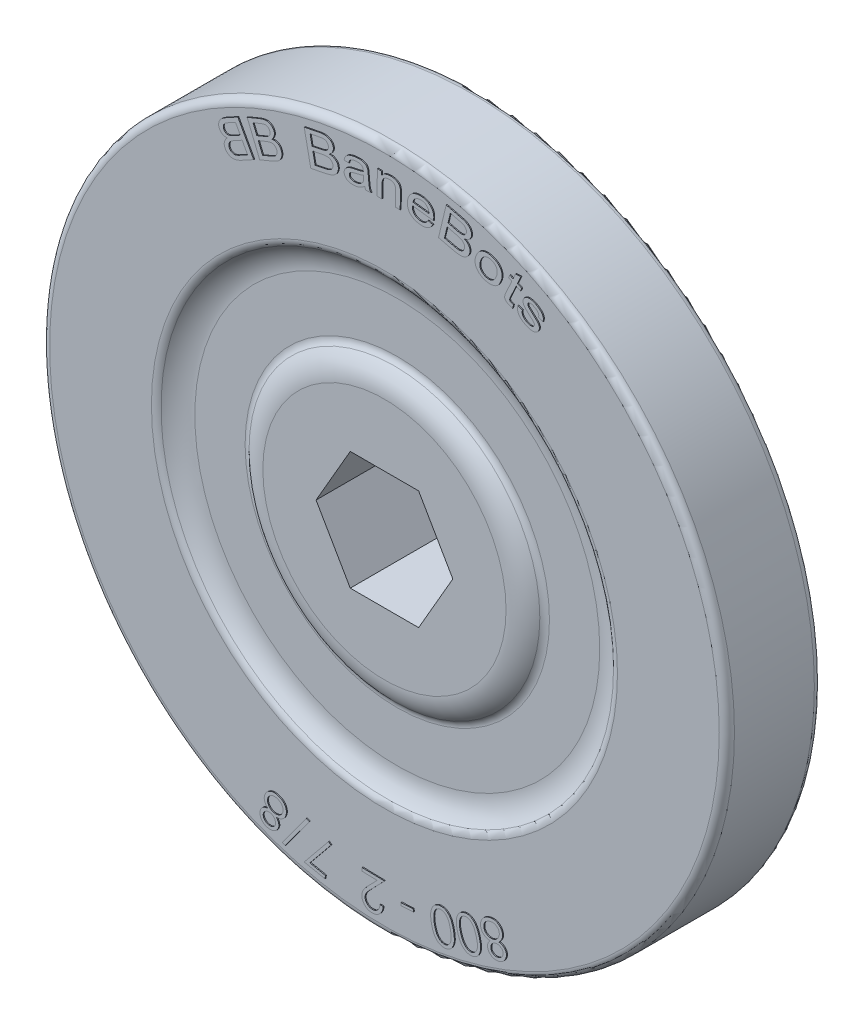
SolidWorks part; units mm, degrees
ref_plane "Front Plane" through (0, 0, 0) normal (0, 0, 1) x (1, 0, 0)
ref_plane "Top Plane" through (0, 0, 0) normal (0, 1, 0) x (1, 0, 0)
ref_plane "Right Plane" through (0, 0, 0) normal (1, 0, 0) x (0, 0, -1)
sketch "Sketch1" plane through (0, 0, 0) normal (0, 0, 1) x (1, 0, 0)
  line L1 (3.594, -6.225) -> (7.188, 0)
  line L2 (7.188, 0) -> (3.594, 6.225)
  line L3 (3.594, 6.225) -> (-3.594, 6.225)
  line L4 (-3.594, 6.225) -> (-7.188, 0)
  line L5 (-7.188, 0) -> (-3.594, -6.225)
  line L6 (-3.594, -6.225) -> (3.594, -6.225)
  circle A0 centre (0, 0) radius 6.225 construction
  circle A1 centre (0, 0) radius 36
  dimension "D1" = 12.45
  dimension "D2" = 72
extrude "Extrude1" add sketch "Sketch1" along normal mid plane 10
fillet "Fillet1" radius 0.8 2 edges at (36, 0, -5) (36, 0, 5)
sketch "Sketch2" plane through (0, 0, 0) normal (0, 1, 0) x (1, 0, 0)
  line L0 (0, 10.15) -> (0, 8.65)
  line L1 (0, 8.65) -> (-15, 8.65)
  line L2 (-15, 8.65) -> (-15, 3.65)
  line L3 (-15, 3.65) -> (-23.5, 3.65)
  line L4 (-23.5, 3.65) -> (-23.5, 10.14)
  line L5 (-23.5, 10.14) -> (-28.5, 10.14)
  line L6 (-28.5, 10.14) -> (-28.5, 10.15)
  line L8 (-28.5, 10.15) -> (0, 10.15)
  dimension "D1" = 0.01
  dimension "D2" = 15
  dimension "D3" = 23.5
  dimension "D4" = 6.5
  dimension "D5" = 1.5
  dimension "D6" = 28.5
revolve "Cut-Revolve1" cut sketch "Sketch2" angle 360 about L0
fillet "Fillet2" radius 1 2 edges at (23.5, 0, -5) (-15, 0, -3.65)
fillet "Fillet3" radius 3.5 2 edges at (-23.5, 0, -3.65) (15, 0, -5)
mirror "Symétrie1" about plane through (0, 0, 0) normal (0, 0, 1) of "Cut-Revolve1", "Fillet2", "Fillet3"
sketch "Sketch4" plane through (0, 0, -5) normal (0, 0, -1) x (-1, 0, 0)
  line L0 (0, 0) -> (-8.33, 29.8599) construction
  line L1 (-13.3409, 27.9825) -> (-15.1484, 31.7737) construction
  line L3 (0, 0) -> (16.4149, 26.2973) construction
  line L4 (0, 0) -> (0, 28.5) construction
  line L5 (0, 0) -> (-16.4149, 26.2973) construction
  line L6 (0, -31) -> (0, 0) construction
  arc A0 (16.4149, 26.2973) -> (-8.33, 29.8599) centre (0, 0) ccw construction
  arc A1 (-10.0963, 29.3098) -> (-16.4149, 26.2973) centre (0, 0) ccw construction
  circle A2 centre (0, 0) radius 35.2 construction
  arc A5 (12.7, -28.2791) -> (-12.7, -28.2791) centre (0, 0) cw construction
  text T0 "BaneBots" font "Arial" height 3.5
  text T1 "800 - 2  7/8"
  dimension "D1" = 62
  dimension "D2" = 25
  dimension "D3" = 7
  dimension "D4" = 1.85
  dimension "D5" = 25.4
extrude "Extrude3" add sketch "Sketch4" along normal blind 0.1
sketch "Sketch5" plane through (0, 0, -5) normal (0, 0, -1) x (-1, 0, 0)
  text T0 "B" font "Arial" height 3.5
extrude "Extrude4" add sketch "Sketch5" along normal blind 0.1
ref_plane "Plane1" through (0, 0, 0) normal (0.9027, -0.4304, 0) x (0, 0, -1)
mirror "Mirror2" about plane through (0, 0, 0) normal (0.9027, -0.4304, 0) of "Extrude4"
sketch "Sketch6" plane through (0, 0, 5) normal (0, 0, 1) x (1, 0, 0)
  line L0 (0, 0) -> (0, 28.5) construction
  arc A0 (-16.4149, 26.2973) -> (-10.0963, 29.3098) centre (0, 0) cw construction
  arc A1 (8.33, 29.8599) -> (-16.4149, 26.2973) centre (0, 0) ccw construction
  arc A2 (16.4149, 26.2973) -> (-8.33, 29.8599) centre (0, 0) ccw construction
  arc A6 (-12.7, -28.2791) -> (12.7, -28.2791) centre (0, 0) ccw
  arc A7 (-12.7, -28.2791) -> (12.7, -28.2791) centre (0, 0) ccw construction
  text T0 "BaneBots" font "Arial" height 3.5
  text T1 "800 - 2  7/8" font "Century Gothic" height 3.5
  dimension "D1" = 7
  dimension "D3" = 0
  dimension "D2" = 25
extrude "Extrude5" add sketch "Sketch6" along normal blind 0.1
sketch "Sketch7" plane through (0, 0, 5) normal (0, 0, 1) x (1, 0, 0)
  line L0 (-13.3409, 27.9825) -> (-15.1484, 31.7737) construction
  arc A2 (-10.0963, 29.3098) -> (-16.4149, 26.2973) centre (0, 0) ccw construction
  circle A3 centre (0, 0) radius 35.2 construction
  text T0 "B" font "Arial" height 3.5
extrude "Extrude6" add sketch "Sketch7" along normal blind 0.1
ref_plane "Plane2" through (0, 0, 0) normal (0.9027, 0.4304, 0) x (0, 0, -1)
mirror "Mirror3" about plane through (0, 0, 0) normal (0.9027, 0.4304, 0) of "Extrude6"
